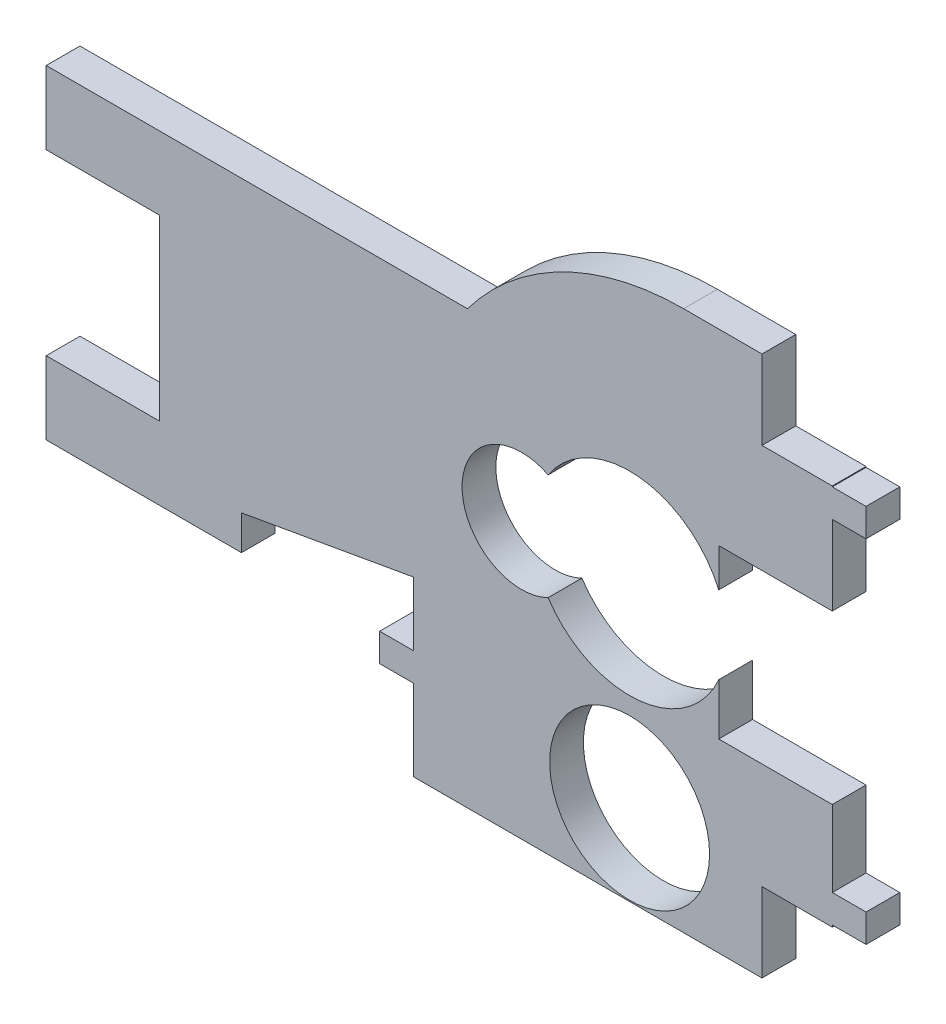
SolidWorks part; units mm, degrees
material "Balsa"
ref_plane "Front Plane" through (0, 0, 0) normal (0, 0, 1) x (1, 0, 0)
ref_plane "Top Plane" through (0, 0, 0) normal (0, 1, 0) x (1, 0, 0)
ref_plane "Right Plane" through (0, 0, 0) normal (1, 0, 0) x (0, 0, -1)
sketch "Sketch1" plane through (0, 0, 0) normal (0, 0, 1) x (1, 0, 0)
  line L0 (0, -1000.1535) -> (0, 48999.8465) construction
  line L1 (0, 9.144) -> (-5.08, 9.144) construction
  line L2 (-1000, 0) -> (49000, 0) construction
  line L3 (9.525, 16.51) -> (11.1125, 16.51)
  line L4 (2.54, 21.59) -> (9.525, 21.59)
  line L5 (-10.16, 8.89) -> (-10.16, -3.81)
  line L6 (-10.16, -3.81) -> (9.525, -3.81)
  line L7 (9.525, 21.59) -> (9.525, -3.81)
  line L8 (-11.7475, 0) -> (-10.16, 0)
  line L9 (-11.7475, 0) -> (-11.7475, 1.3208)
  line L10 (-11.7475, 1.3208) -> (-10.16, 1.3208)
  line L11 (-10.16, 0) -> (-10.16, 1.3208)
  line L12 (9.525, 0) -> (11.1125, 0)
  line L13 (9.525, 0) -> (9.525, 1.3208)
  line L14 (9.525, 1.3208) -> (11.1125, 1.3208)
  line L15 (11.1125, 0) -> (11.1125, 1.3208)
  line L16 (9.525, 16.51) -> (9.525, 17.8308)
  line L17 (9.525, 17.8308) -> (11.1125, 17.8308)
  line L18 (11.1125, 16.51) -> (11.1125, 17.8308)
  line L19 (-7.62, 16.51) -> (-27.4189, 16.51)
  line L20 (-27.4189, 16.51) -> (-27.4189, 1.27)
  line L21 (-27.4189, 1.27) -> (-10.16, 4.318)
  line L22 (9.525, 8.89) -> (-35.5862, 8.89) construction
  line L23 (-27.4189, 1.27) -> (-18.2418, 1.27)
  line L24 (-27.4189, 13.081) -> (-22.0849, 13.081)
  line L25 (-27.4189, 13.081) -> (-27.4189, 4.699)
  line L26 (-27.4189, 4.699) -> (-22.0849, 4.699)
  line L27 (-22.0849, 13.081) -> (-22.0849, 4.699)
  line L28 (-18.2418, 1.27) -> (-18.2418, 2.8907)
  line L30 (9.525, 12.7762) -> (4.191, 12.7762)
  line L31 (9.525, 12.7762) -> (9.525, 4.9022)
  line L32 (9.525, 4.9022) -> (4.191, 4.9022)
  line L33 (4.191, 12.7762) -> (4.191, 4.9022)
  circle A0 centre (0, 0) radius 3.7592
  arc A1 (-3.829, 6.6457) -> (-3.829, 11.6423) centre (0, 9.144) ccw
  arc A2 (-3.829, 11.6423) -> (-3.829, 6.6457) centre (-5.08, 9.144) ccw
  arc A3 (2.54, 21.59) -> (-10.16, 8.89) centre (2.54, 8.89) ccw
  point P33 (9.525, 8.89)
  point P35 (-27.4189, 8.89)
  point P41 (-27.4189, 8.89)
  dimension "D1" = 7.5184
  dimension "D4" = 3.81
  dimension "D3" = 9.144
  dimension "D5" = 2.794
  dimension "D9" = 12.7
  dimension "D10" = 1.5875
  dimension "D2" = 25.4
  dimension "D6" = 9.525
  dimension "D7" = 5.08
  dimension "D8" = 19.685
  dimension "D11" = 9.144
  dimension "D12" = 1.3208
  dimension "D13" = 1.3208
  dimension "D14" = 1.5875
  dimension "D15" = 2
  dimension "D16" = 8.128
  dimension "D17" = 15.24
  dimension "D18" = 17.526
  dimension "D19" = 8.382
  dimension "D20" = 5.334
  dimension "D21" = 5.334
  dimension "D22" = 8.8138
  dimension "D23" = 7.874
extrude "Boss-Extrude1" add sketch "Sketch1" along normal blind 1.5875 contours L4 A3 L5 L6 L7 A0 A2 A1 | L10 L9 L8 L5 | L3 L18 L17 L7 | L12 L15 L14 L7 | A3 L19 L20 L21 L5 | L23 L28 L21 region at (10.3187, 17.1704, 0) region at (9.2036, 14.6431, 0) region at (10.3187, 0.6604, 0) region at (-17.5342, 9.9456, 0) region at (-10.9538, 0.6604, 0) region at (-21.3008, 1.8102, 0)
sketch "Sketch2" plane through (0, 0, 1.5875) normal (0, 0, 1) x (1, 0, 0)
  line L1 (6.223, -3.8481) -> (9.525, -3.8481)
  line L2 (6.223, -3.8481) -> (6.223, -0.0889)
  line L3 (6.223, -0.0889) -> (9.525, -0.0889)
  line L4 (9.525, -3.8481) -> (9.525, -0.0889)
  line L5 (9.525, -0.9144) -> (9.525, -3.0226)
  line L7 (9.525, 20.8026) -> (9.525, 18.6944)
  line L9 (6.223, 17.8689) -> (9.525, 17.8689)
  line L10 (6.223, 17.8689) -> (6.223, 21.6281)
  line L11 (6.223, 21.6281) -> (9.525, 21.6281)
  line L12 (9.525, 17.8689) -> (9.525, 21.6281)
  point P8 (9.525, -1.9685)
  point P9 (9.525, -1.9685)
  point P10 (9.525, 19.7485)
  point P15 (9.525, 19.7485)
  line M4 (9.525, 21.59) -> (2.54, 21.59)
  line M11 (-10.16, -3.81) -> (9.525, -3.81)
  line M12 (9.525, -3.81) -> (9.525, 0)
  dimension "D1" = 3.7592
  dimension "D2" = 3.302
  dimension "D3" = 3.7592
  dimension "D4" = 3.302
extrude "Cut-Extrude1" cut sketch "Sketch2" against normal up to next contours L3 L2 L4 M11 M12 | L10 L9 M4 region at (7.874, -1.9495, 1.5875) region at (7.874, 19.7294, 1.5875)
move or copy body "Body-Move/Copy1" [suppressed] bodies to move or copy 102
